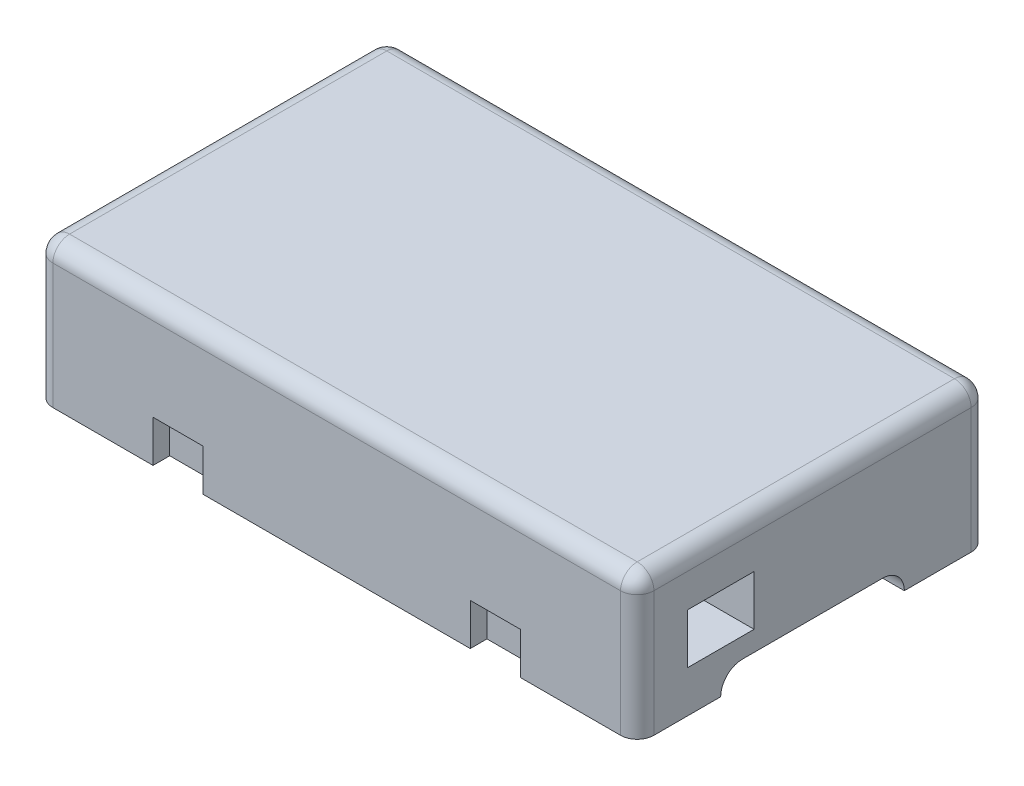
SolidWorks part; units mm, degrees
ref_plane "Front Plane" through (0, 0, 0) normal (0, 0, 1) x (1, 0, 0)
ref_plane "Top Plane" through (0, 0, 0) normal (0, 1, 0) x (1, 0, 0)
ref_plane "Right Plane" through (0, 0, 0) normal (1, 0, 0) x (0, 0, -1)
sketch "Sketch1" plane through (0, 0, 0) normal (0, 1, 0) x (1, 0, 0)
  line L1 (-18, 10.5) -> (18, 10.5)
  line L2 (-18, 10.5) -> (-18, -10.5)
  line L3 (-18, -10.5) -> (18, -10.5)
  line L4 (18, 10.5) -> (18, -10.5)
  line L5 (-18, 10.5) -> (18, -10.5) construction
  line L6 (-18, -10.5) -> (18, 10.5) construction
  point P0 (0, 0)
  dimension "D1" = 21
  dimension "D2" = 36
extrude "Boss-Extrude2" add sketch "Sketch1" along normal blind 15
sketch "Sketch2" plane through (18, 0, 0) normal (1, 0, 0) x (0, 0, -1)
  line L0 (-4.2, 6.5) -> (4.2, 6.5) construction
  line L1 (-4.2, 7.8) -> (4.2, 7.8)
  line L2 (-4.2, 5.2) -> (4.2, 5.2)
  line L4 (10.5, 15) -> (10.5, 0) construction
  line L5 (-10.5, 0) -> (10.5, 0) construction
  arc A0 (-4.2, 7.8) -> (-4.2, 5.2) centre (-4.2, 6.5) ccw
  arc A1 (4.2, 5.2) -> (4.2, 7.8) centre (4.2, 6.5) ccw
  point P2 (0, 6.5)
  dimension "D1" = 10.5
  dimension "D2" = 6.5
  dimension "D3" = 8.4
  dimension "D4" = 1.3
extrude "Cut-Extrude1" cut sketch "Sketch2" against normal blind 15
ref_plane "Plane2" through (0, 6.5, 0) normal (0, 1, 0) x (1, 0, 0)
split "Split1" trim tools "Plane2" bodies to split 103 resulting bodies 104 105
sketch "Sketch5" plane through (0, 6.5, 0) normal (0, 1, 0) x (1, 0, 0)
  line L0 (-18, 10.5) -> (-18, -10.5) construction
  line L1 (-15, 7.5) -> (15, 7.5)
  line L2 (-15, 7.5) -> (-15, -7.5)
  line L3 (-15, -7.5) -> (15, -7.5)
  line L4 (15, 7.5) -> (15, -7.5)
  line L5 (18, 5.5) -> (18, 10.5) construction
  line L6 (18, 10.5) -> (-18, 10.5) construction
  line L7 (-18, -10.5) -> (18, -10.5) construction
  dimension "D1" = 3
  dimension "D2" = 3
  dimension "D3" = 3
  dimension "D4" = 3
extrude "Cut-Extrude2" cut sketch "Sketch5" against normal blind 3.5
sketch "Sketch7" plane through (0, 6.5, 0) normal (0, -1, 0) x (1, 0, 0)
  line L0 (-18, -10.5) -> (-18, 10.5) construction
  line L1 (-15, 7.5) -> (15, 7.5)
  line L2 (-15, 7.5) -> (-15, -7.5)
  line L3 (-15, -7.5) -> (15, -7.5)
  line L4 (15, 7.5) -> (15, -7.5)
  line L5 (18, 10.5) -> (18, 5.5) construction
  line L6 (-18, 10.5) -> (18, 10.5) construction
  line L7 (18, -10.5) -> (-18, -10.5) construction
  dimension "D1" = 3
  dimension "D2" = 3
  dimension "D3" = 3
  dimension "D4" = 3
extrude "Cut-Extrude3" cut sketch "Sketch7" against normal blind 5.5
fillet "Fillet1" radius 1 8 edges at (-18, 10.75, -10.5) (-18, 10.75, 10.5) (18, 10.75, 10.5) (18, 10.75, -10.5) (-18, 15, 0) (0, 15, 10.5) (18, 15, 0) (0, 15, -10.5)
fillet "Fillet2" radius 1 8 edges at (18, 3.25, 10.5) (18, 3.25, -10.5) (18, 0, 0) (0, 0, -10.5) (-18, 3.25, -10.5) (-18, 0, 0) (0, 0, 10.5) (-18, 3.25, 10.5)
sketch "Sketch9" plane through (0, 0, 10.5) normal (0, 0, 1) x (1, 0, 0)
  line L0 (0, 0) -> (0, 10.1823) construction
  line L1 (11.55, 6.5) -> (-11.55, 6.5) construction
  line L2 (-11, 6.5) -> (-8, 6.5)
  line L3 (-11, 6.5) -> (-11, 9.5)
  line L4 (-11, 9.5) -> (-8, 9.5)
  line L5 (-8, 6.5) -> (-8, 9.5)
  line L6 (11, 6.5) -> (11, 9.5)
  line L7 (8, 6.5) -> (8, 9.5)
  line L8 (11, 9.5) -> (8, 9.5)
  line M7 (17, 6.5) -> (-17, 6.5)
  dimension "D1" = 3
  dimension "D2" = 8
  dimension "D3" = 0
  dimension "D4" = 3
extrude "Boss-Extrude3" add sketch "Sketch9" against normal blind 1 contours L5 L4 L3 L2
extrude "Boss-Extrude4" add sketch "Sketch9<4>" against normal blind 1 contours L6 L8 L7 M7 region at (9.5, 8, 10.5)
sketch "Sketch9<4>" plane through (0, 0, 10.5) normal (0, 0, 1) x (1, 0, 0) same geometry as "Sketch9"
sketch "Sketch10" plane through (0, 0, 9.5) normal (0, 0, -1) x (-1, 0, 0)
  line L0 (-8, 6.5) -> (-8, 9.5) construction
  line L1 (-11, 9.5) -> (-8, 9.5)
  line L2 (-11, 9.5) -> (-11, 8)
  line L3 (-11, 8) -> (-8, 8)
  line L4 (-8, 9.5) -> (-8, 8)
  line L5 (8, 6.5) -> (8, 9.5) construction
  line L6 (8, 9.5) -> (11, 9.5)
  line L7 (8, 9.5) -> (8, 8)
  line L8 (8, 8) -> (11, 8)
  line L9 (11, 9.5) -> (11, 8)
  line L10 (11, 6.5) -> (11, 9.5) construction
extrude "Boss-Extrude5" add sketch "Sketch10" along normal blind 1
sketch "Sketch11" plane through (11, 0, 0) normal (1, 0, 0) x (0, 0, -1)
  line L0 (-9.5, 9.5) -> (-8.5, 8)
  line L1 (-8.5, 9.5) -> (-10.5, 9.5) construction
  line L2 (-8.5, 9.5) -> (-8.5, 8) construction
  line L3 (-8.5, 8) -> (-8.5, 9.5)
  line L4 (-8.5, 9.5) -> (-9.5, 9.5)
extrude "Cut-Extrude4" cut sketch "Sketch11" against normal through all
sketch "Sketch12" plane through (0, 0, -10.5) normal (0, 0, -1) x (-1, 0, 0)
  line L0 (0, 0) -> (0, 15.2889) construction
  line L1 (11.55, 6.5) -> (-11.55, 6.5) construction
  line L2 (-1.5, 9.5) -> (1.5, 9.5)
  line L3 (-1.5, 9.5) -> (-1.5, 3.5)
  line L4 (-1.5, 3.5) -> (1.5, 3.5)
  line L5 (1.5, 9.5) -> (1.5, 3.5)
  line L6 (-1.5, 9.5) -> (1.5, 3.5) construction
  line L7 (-1.5, 3.5) -> (1.5, 9.5) construction
  point P1 (0, 6.5)
  dimension "D1" = 6
  dimension "D2" = 3
extrude "Boss-Extrude6" add sketch "Sketch12" along normal mid plane 1
fillet "Fillet3" radius 11 1 edges at (0, 3.5, -11)
fillet "Fillet4" radius 0.5 4 edges at (9.5, 9.5, 9.5) (-9.5, 9.5, 9.5) (-9.5, 9.5, 10.5) (9.5, 9.5, 10.5)
sketch "Sketch17" plane through (0, 0, -10) normal (0, 0, 1) x (1, 0, 0)
  line L1 (-1.5, 9.5) -> (1.5, 9.5)
  line L2 (-1.5, 9.5) -> (-1.5, 11.5)
  line L3 (-1.5, 11.5) -> (1.5, 11.5)
  line L4 (1.5, 9.5) -> (1.5, 11.5)
  dimension "D1" = 3
  dimension "D2" = 2
extrude "Boss-Extrude7" add sketch "Sketch17" against normal blind 1
sketch "Sketch18" plane through (0, 0, -10) normal (0, 0, 1) x (1, 0, 0)
  line L0 (-1.5, 6.5) -> (-1.5, 11.5) construction
  line L1 (-1.5, 10) -> (1.5, 10)
  line L2 (-1.5, 10) -> (-1.5, 8.5)
  line L3 (-1.5, 8.5) -> (1.5, 8.5)
  line L4 (1.5, 10) -> (1.5, 8.5)
  line L5 (1.5, 11.5) -> (1.5, 6.5) construction
  line L6 (11.825, 6.5) -> (-11.825, 6.5) construction
  dimension "D1" = 1.5
  dimension "D2" = 2
extrude "Boss-Extrude8" add sketch "Sketch18" along normal blind 1
fillet "Fillet5" radius 0.75 2 edges at (0, 8.5, -9) (0, 10, -9)
fillet "Fillet6" radius 1 1 edges at (0, 11.5, -10) conic radius 10
combine bodies "Combine1" operation type subtract main body 107 bodies to subtract 114
sketch "Sketch19" plane through (0, 0, 10.5) normal (0, 0, 1) x (1, 0, 0)
  line L1 (8, 9) -> (11, 9)
  line L2 (8, 9) -> (8, 8)
  line L3 (8, 8) -> (11, 8)
  line L4 (11, 9) -> (11, 8)
  line L5 (-11, 9) -> (-8, 9)
  line L6 (-11, 9) -> (-11, 8)
  line L7 (-11, 8) -> (-8, 8)
  line L8 (-8, 9) -> (-8, 8)
extrude "Cut-Extrude5" cut sketch "Sketch19" against normal blind 8
sketch "Sketch20" plane through (0, 0, -10.5) normal (0, 0, -1) x (-1, 0, 0)
  line L1 (1.5, 8.5) -> (-1.5, 8.5)
  line L2 (1.5, 8.5) -> (1.5, 11.0659)
  line L3 (1.5, 11.0659) -> (-1.5, 11.0659)
  line L4 (-1.5, 8.5) -> (-1.5, 11.0659)
extrude "Cut-Extrude6" cut sketch "Sketch20" against normal blind 8
sketch "Sketch21" plane through (18, 0, 0) normal (1, 0, 0) x (0, 0, -1)
  line L0 (-9.5, 14) -> (-9.5, 6.5) construction
  line L1 (-7.5, 12) -> (-3.5, 12)
  line L2 (-7.5, 12) -> (-7.5, 9)
  line L3 (-7.5, 9) -> (-3.5, 9)
  line L4 (-3.5, 12) -> (-3.5, 9)
  line L6 (9.5, 14) -> (-9.5, 14) construction
  dimension "D1" = 3
  dimension "D2" = 4
  dimension "D3" = 2
  dimension "D4" = 2
extrude "Cut-Extrude7" cut sketch "Sketch21" against normal blind 8
